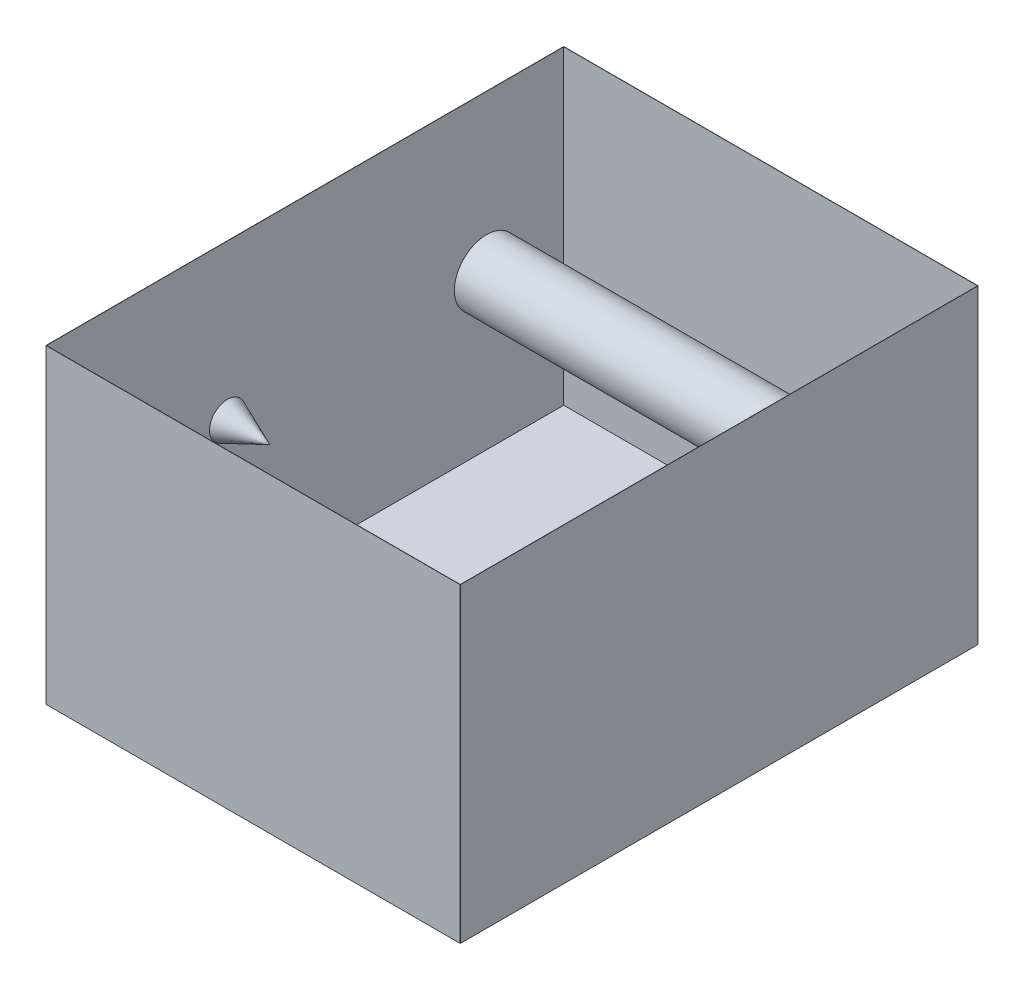
SolidWorks part; units mm, degrees
ref_plane "Front Plane" through (0, 0, 0) normal (0, 0, 1) x (1, 0, 0)
ref_plane "Top Plane" through (0, 0, 0) normal (0, 1, 0) x (1, 0, 0)
ref_plane "Right Plane" through (0, 0, 0) normal (1, 0, 0) x (0, 0, -1)
sketch "Sketch1" plane through (0, 0, 0) normal (0, 1, 0) x (1, 0, 0)
  line L0 (0, 174.3662) -> (0, -177.7465) construction
  line L1 (-162.2535, 3.3803) -> (373.5211, 3.3803) construction
  line L2 (-80, 103.3803) -> (-80, -96.6197)
  line L3 (-80, -96.6197) -> (80, -96.6197)
  line L4 (80, -96.6197) -> (80, 103.3803)
  line L5 (80, 103.3803) -> (-80, 103.3803)
  point P7 (0, 103.3803)
  point P10 (-80, 3.3803)
  dimension "D1" = 200
  dimension "D2" = 160
extrude "Boss-Extrude1" add sketch "Sketch1" along normal blind 120
shell "Shell1" thickness 0.1 removed face at (0, 120, -3.3803) outward yes
sketch "Sketch2" plane through (80.1, 0, 0) normal (1, 0, 0) x (0, 0, -1)
  line L0 (-7.6224, 60) -> (120.5269, 60) construction
  line L1 (73.4803, 131.6834) -> (73.4803, -12.4307) construction
  line L2 (-96.7197, 120) -> (103.4803, 120) construction
  line L3 (103.4803, 120) -> (103.4803, -0.1) construction
  circle A0 centre (73.4803, 59.6264) radius 12.5
  dimension "D3" = 25
  dimension "D1" = 60
  dimension "D2" = 30
extrude "Boss-Extrude2" add sketch "Sketch2" against normal blind 160
fillet "Fillet3" radius 0.1 4 edges at (80.1, 59.95, 96.7197) (-80.1, 59.95, 96.7197) (80.1, 59.95, -103.4803) (-80.1, 59.95, -103.4803)
sketch "Sketch3" plane through (-80.1, 0, 0) normal (-1, 0, 0) x (0, 0, 1)
  line L0 (-114.0547, 60) -> (121.533, 60) construction
  line L1 (26.6197, 134.4881) -> (26.6197, -21.276) construction
  line L2 (-103.3803, 120) -> (96.6197, 120) construction
  line L4 (96.6197, -0.1) -> (96.6197, 120) construction
  circle A0 centre (26.6197, 60) radius 7
  dimension "D3" = 14
  dimension "D1" = 60
  dimension "D2" = 70
extrude "Boss-Extrude3" add sketch "Sketch3" against normal blind 90 draft 23
sketch "Sketch5" plane through (80, 0, 0) normal (-1, 0, 0) x (0, 0, 1)
  line L0 (134.1776, 60) -> (-122.3636, 60) construction
  line L1 (26.6197, -14.6486) -> (26.6197, 140.6671) construction
  line L2 (96.6197, 120) -> (96.6197, 0) construction
  line L3 (96.6197, 120) -> (-103.3803, 120) construction
  circle A0 centre (26.6197, 60) radius 7
  dimension "D1" = 70
  dimension "D2" = 60
extrude "Boss-Extrude4" add sketch "Sketch5" along normal blind 90 draft 23
